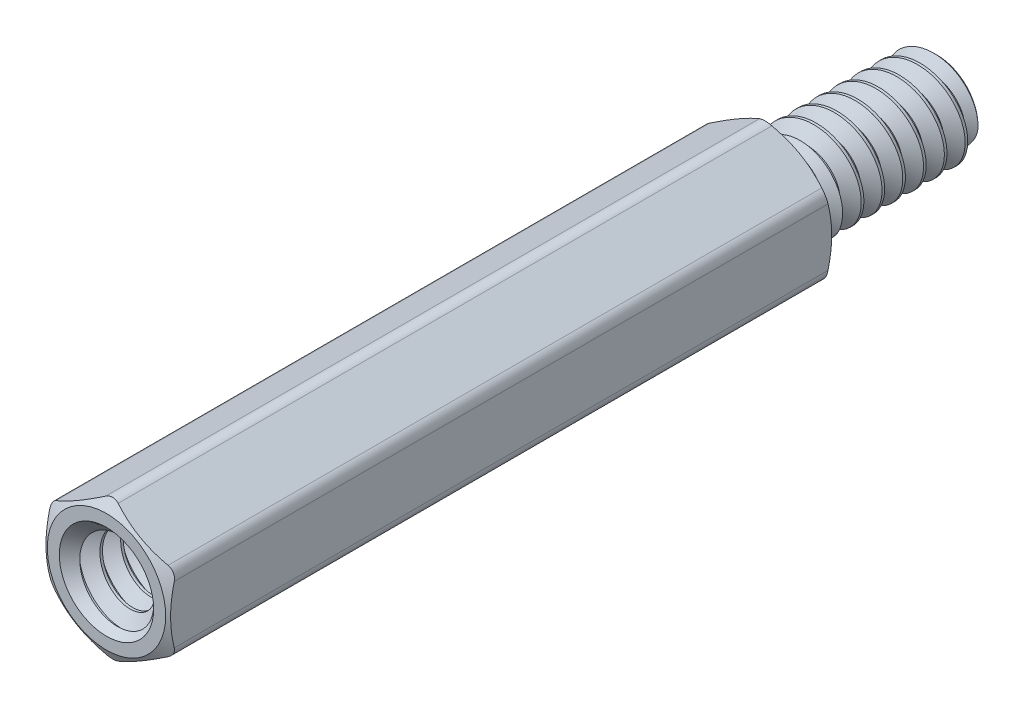
SolidWorks part; units mm, degrees
ref_plane "Front Plane" through (0, 0, 0) normal (0, 0, 1) x (1, 0, 0)
ref_plane "Top Plane" through (0, 0, 0) normal (0, 1, 0) x (1, 0, 0)
ref_plane "Right Plane" through (0, 0, 0) normal (1, 0, 0) x (0, 0, -1)
sketch "Sketch1" plane through (0, 0, 0) normal (0, 0, 1) x (1, 0, 0)
  line L1 (2.3813, 1.3748) -> (0, 2.7496)
  line L2 (0, 2.7496) -> (-2.3812, 1.3748)
  line L3 (-2.3812, 1.3748) -> (-2.3812, -1.3748)
  line L4 (-2.3812, -1.3748) -> (0, -2.7496)
  line L5 (0, -2.7496) -> (2.3813, -1.3748)
  line L6 (2.3813, -1.3748) -> (2.3813, 1.3748)
  circle A0 centre (0, 0) radius 2.3812 construction
  point P10 (0, -2.3812)
  dimension "Hex Size" = 4.7625
sketch "Sketch2" plane through (0, 0, 0) normal (1, 0, 0) x (0, 0, -1)
  line L0 (6.35, 0) -> (-25.4, 0) construction
  line L2 (0, 1.7526) -> (0, -1.7526) construction
  line L3 (-15.875, 1.7526) -> (-15.875, -1.7526) construction
  line L4 (-26.1441, 1.8385) -> (-25.7473, 1.1511) construction
  line L5 (-25.7473, 1.1511) -> (-25.3504, 1.8385) construction
  line L6 (-25.3504, 1.8385) -> (-26.1441, 1.8385) construction
  line L7 (-26.0945, 1.7526) -> (-25.4, 1.7526) construction
  line L8 (-25.7969, 1.237) -> (-25.6977, 1.237) construction
  line L9 (-25.7473, 1.237) -> (-25.7473, 1.1511) construction
  line L10 (-25.7473, 1.7526) -> (-25.7473, 1.8385) construction
  line L11 (6.3004, 1.8385) -> (7.0941, 1.8385) construction
  line L12 (7.0941, 1.8385) -> (6.6973, 1.1511) construction
  line L13 (6.6973, 1.1511) -> (6.3004, 1.8385) construction
  line L14 (6.35, 1.7526) -> (7.0445, 1.7526) construction
  line L15 (6.6477, 1.237) -> (6.7469, 1.237) construction
  line L16 (6.6973, 1.237) -> (6.6973, 1.1511) construction
  line L17 (6.6973, 1.7526) -> (6.6973, 1.8385) construction
  line L18 (0, 2.7496) -> (-25.4, 2.7496) construction
  point P6 (0, 0)
  point P9 (-15.875, 0)
  dimension "Length" = 25.4
sketch "Sketch3" plane through (0, 0, 0) normal (1, 0, 0) x (0, 0, -1)
  line L0 (-15.875, 0) -> (6.35, 0)
  line L1 (-15.875, 1.7526) -> (-15.875, -1.7526) construction
  line L2 (6.35, 0) -> (6.35, 1.5542)
  line L3 (6.35, 1.5542) -> (6.1516, 1.7526)
  line L4 (6.1516, 1.7526) -> (1.0597, 1.7526)
  line L5 (1.0597, 1.7526) -> (0.762, 1.237)
  line L6 (-15.875, 0) -> (-15.875, 1.5542)
  line L7 (-15.875, 1.5542) -> (-16.0734, 1.7526)
  line L8 (-16.0734, 1.7526) -> (-25.2016, 1.7526)
  line L9 (-25.2016, 1.7526) -> (-25.4, 1.951)
  line L10 (6.1516, 0) -> (6.1516, -1.7526) construction
  line L11 (-25.4, 1.951) -> (-25.4, 2.3812)
  line L12 (-25.4, 2.3812) -> (0, 2.3812)
  line L14 (0.762, 1.237) -> (0.1984, 1.237)
  line L15 (0, 1.4355) -> (0, 2.3812)
  arc A0 (0, 1.4355) -> (0.1984, 1.237) centre (0.1984, 1.4355) ccw
  point P5 (-25.4, -2.3812)
  point P8 (-23.4156, -1.7526)
  point P9 (4.3656, -1.7526)
  point P27 (0, 1.237)
  dimension "D4" = 0.1984
  dimension "D2" = 0.1984
  dimension "D1" = 45
  dimension "D6" = 1.9844
  dimension "D7" = 60
  dimension "D3" = 1.9844
  dimension "D5" = 0.762
revolve "Revolve1" add sketch "Sketch3" angle 360 about L0
sketch "Sketch4" plane through (0, 0, 25.4) normal (0, 0, 1) x (1, 0, 0)
  line L0 (0, 2.3812) -> (0, 1.7526) construction
  line L1 (-2.3812, 1.3748) -> (-2.3812, -1.3748)
  line L2 (-2.3812, -1.3748) -> (0, -2.7496)
  line L3 (0, -2.7496) -> (2.3812, -1.3748)
  line L4 (2.3812, -1.3748) -> (2.3812, 1.3748)
  line L5 (2.3812, 1.3748) -> (0, 2.7496)
  line L6 (0, 2.7496) -> (-2.3812, 1.3748)
  circle A0 centre (0, 0) radius 2.3812 construction
  circle A1 centre (0, 0) radius 2.0669
  circle A2 centre (0, 0) radius 2.3812 construction
  point P16 (0, 2.0669)
extrude "Boss-Extrude1" add sketch "Sketch4" against normal up to surface (25.4 mm away) up to face at (0, 2.3812, 0)
sketch "Sketch5" plane through (0, 0, 25.4) normal (0, 0, 1) x (1, 0, 0)
  line L0 (-1.0053, 1.4356) -> (1.0053, -1.4356) construction
  line L1 (0, 1.7526) -> (0, -1.7526) construction
  line L3 (0, -3.9247) -> (0, 3.9247) construction
  circle A0 centre (0, 0) radius 2.2622
  point P11 (1.0053, -1.4356)
  dimension "D1" = 4.5244
  dimension "D2" = 35
extrude "Cut-Extrude1" cut sketch "Sketch5" against normal through all draft 60 flip side to cut
sketch "Sketch6" plane through (0, 0, 0) normal (0, 0, -1) x (-1, 0, 0)
  circle A0 centre (0, 0) radius 2.2622
  circle A1 centre (0, 0) radius 2.2622 construction
extrude "Cut-Extrude2" cut sketch "Sketch6" against normal through all draft 60 flip side to cut
fillet "Fillet1" radius 0.4763 6 edges at (0, 2.7496, 12.7) (-2.3812, -1.3748, 12.7) (0, -2.7496, 12.7) (2.3812, -1.3748, 12.7) (2.3812, 1.3748, 12.7) (-2.3812, 1.3748, 12.7)
sketch "Drawing1" plane through (0, 0, 0) normal (1, 0, 0) x (0, 0, -1)
  line L0 (-25.4, 1.7526) -> (-15.875, 1.7526) construction
  line L1 (-15.875, 1.7526) -> (-15.875, -1.7526) construction
  line L2 (-15.875, -1.7526) -> (-25.4, -1.7526) construction
sketch "Sketch7" plane through (0, 0, 0) normal (-1, 0, 0) x (0, 0, 1)
  line L0 (-6.6477, 1.237) -> (-6.7469, 1.237)
  line L1 (-6.7469, 1.237) -> (-7.0693, 1.7956)
  line L2 (-7.0941, 1.8385) -> (-6.6973, 1.1511) construction
  line L3 (-7.0693, 1.7956) -> (-6.3252, 1.7956)
  line L4 (-6.6973, 1.1511) -> (-6.3004, 1.8385) construction
  line L5 (-6.3252, 1.7956) -> (-6.6477, 1.237)
  line L6 (-6.6973, 1.7526) -> (-6.6973, 1.8385) construction
  point P12 (-6.6973, 1.7956)
sketch "Sketch8" plane through (0, 0, -6.35) normal (0, 0, -1) x (-1, 0, 0)
  circle A0 centre (0, 0) radius 1.7526
curve "Helix/Spiral1" pitch 0.7937 height 6.1595 turns 7.76
sweep "Cut-Sweep1" cut profiles "Sketch7" path "Helix/Spiral1" align with end faces yes
sketch "Sketch9" plane through (0, 0, 15.875) normal (0, 0, 1) x (1, 0, 0)
  circle A0 centre (0, 0) radius 1.951
extrude "Boss-Extrude2" add sketch "Sketch9" along normal up to surface (9.525 mm away) up to face at (0, 1.951, 25.4)
sketch "Sketch10" plane through (0, 0, 0) normal (1, 0, 0) x (0, 0, -1)
  line L0 (6.35, 0) -> (-25.4, 0) construction
  line L1 (-15.875, 1.7526) -> (-25.4, 1.7526)
  line L2 (-15.875, 1.7526) -> (-15.875, 0)
  line L3 (-15.875, 0) -> (-25.4, 0)
  line L4 (-25.4, 1.7526) -> (-25.4, 0)
revolve "Revolve2" add sketch "Sketch10" angle 360 about L0
sketch "Sketch11" plane through (0, 0, 25.4) normal (0, 0, 1) x (1, 0, 0)
  circle A0 centre (0, 0) radius 1.7526
  circle A1 centre (0, 0) radius 1.7526 construction
sketch "Sketch12" plane through (0, 0, 0) normal (1, 0, 0) x (0, 0, -1)
  line L0 (-25.7969, 1.237) -> (-25.6977, 1.237)
  line L1 (-25.6977, 1.237) -> (-25.3752, 1.7956)
  line L2 (-25.7473, 1.1511) -> (-25.3504, 1.8385) construction
  line L3 (-25.3752, 1.7956) -> (-26.1193, 1.7956)
  line L4 (-26.1441, 1.8385) -> (-25.7473, 1.1511) construction
  line L5 (-26.1193, 1.7956) -> (-25.7969, 1.237)
  line L6 (-25.7473, 1.7526) -> (-25.7473, 1.8385) construction
  point P12 (-25.7473, 1.7956)
curve "Helix/Spiral2" pitch 0.7937 height 10.3187 turns 13
sweep "Cut-Sweep2" cut profiles "Sketch12" path "Helix/Spiral2" align with end faces yes
combine bodies "Combine1" operation type subtract main body 113 bodies to subtract 114
sketch "Sketch13" plane through (0, 0, 25.4) normal (0, 0, 1) x (1, 0, 0)
  circle A0 centre (0, 0) radius 1.8034
  dimension "D1" = 0.0508
extrude "Cut-Extrude3" cut sketch "Sketch13" against normal through all draft 45
equation "\"Thread Pitch (B)/8@Sketch2\"=\"Thread Pitch (B)@Sketch2\"/8"
equation "\"Thread Pitch (A)/8@Sketch2\"=\"Thread Pitch (A)@Sketch2\"/8"
equation "\"D1@Sketch5\" = \"Hex Size@Sketch1\" * .95"
equation "\"D1@Fillet1\" = \"Hex Size@Sketch1\" * .1"
equation "\"D2@Sketch3\" = \"Thread Pitch (A)@Sketch2\" * .25"
equation "\"D4@Sketch3\" = \"D2@Sketch3\""
equation "\"D6@Sketch3\" = \"Thread Pitch (A)@Sketch2\" * 2.5"
equation "\"D3@Helix/Spiral1\" = \"Thread Length (A)@Sketch2\" - \"D5@Sketch3\" * .25"
equation "\"D4@Helix/Spiral1\" = \"Thread Pitch (A)@Sketch2\""
equation "\"D3@Sketch3\" = \"Thread Pitch (B)@Sketch2\" * 2.5"
equation "\"D5@Sketch3\" = \"Thread Length (A)@Sketch2\" * .12"
equation "\"D3@Helix/Spiral2\" = \"Minimum Thread Length (B)@Sketch2\" + \"Thread Pitch (B)@Sketch2\""
equation "\"D4@Helix/Spiral2\" = \"Thread Pitch (B)@Sketch2\""
